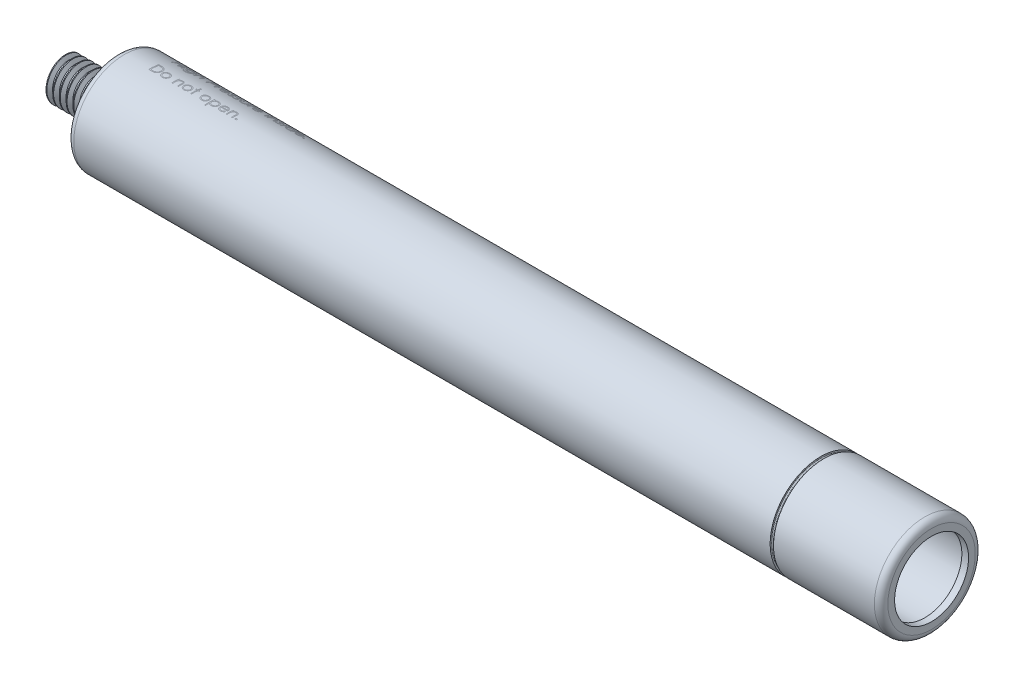
SolidWorks part; units mm, degrees
material "AISI 1020"
ref_plane "Ön Düzlem" through (0, 0, 0) normal (0, 0, 1) x (1, 0, 0)
ref_plane "Üst Düzlem" through (0, 0, 0) normal (0, 1, 0) x (1, 0, 0)
ref_plane "Sağ Düzlem" through (0, 0, 0) normal (1, 0, 0) x (0, 0, -1)
sketch "Çizim1" plane through (0, 0, 0) normal (0, 0, 1) x (1, 0, 0)
  line L0 (0, 3) -> (0, 6.5)
  line L1 (1, 7.5) -> (104.5, 7.5)
  line L8 (0, 0) -> (121, 0) construction
  line L9 (121, 6.5) -> (121, 5.5)
  line L10 (121, 5.5) -> (120, 5.5)
  line L11 (120, 5.5) -> (120, 6)
  line L12 (120, 6) -> (2, 6)
  line L13 (1, 5) -> (1, 0)
  line L14 (105, 7.5) -> (120, 7.5)
  line L16 (104.5, 7.5) -> (104.5, 7.3)
  line L17 (104.65, 7.15) -> (104.85, 7.15)
  line L18 (105, 7.5) -> (105, 7.3)
  line L19 (0, 0) -> (1, 0)
  line L20 (0, 3) -> (-8, 3)
  line L21 (-8, 3) -> (-8, 0)
  line L22 (-8, 0) -> (0, 0)
  arc A0 (120, 7.5) -> (121, 6.5) centre (120, 6.5) cw
  arc A1 (0, 6.5) -> (1, 7.5) centre (1, 6.5) cw
  arc A2 (2, 6) -> (1, 5) centre (2, 5) ccw
  arc A3 (104.5, 7.3) -> (104.65, 7.15) centre (104.65, 7.3) ccw
  arc A4 (104.85, 7.15) -> (105, 7.3) centre (104.85, 7.3) ccw
  point P12 (121, 7.5)
  point P19 (0, 7.5)
  point P28 (104.5, 7.15)
  point P31 (105, 7.15)
  dimension "D9" = 1
  dimension "D10" = 1
  dimension "D13" = 0.15
  dimension "D1" = 121
  dimension "D2" = 7.5
  dimension "D3" = 1.5
  dimension "D4" = 1
  dimension "D5" = 5.5
  dimension "D6" = 1
  dimension "D7" = 0.5
  dimension "D8" = 16
  dimension "D11" = 3
  dimension "D12" = 8
revolve "Döndür1" add sketch "Çizim1" angle 360 about L8
thread "Diş1" pitch 1 method cut trim with start face yes trim with end face yes profile "Diş Profili1" start angle 0, offset 1, length 0, pitch 1, diameter 6
ref_plane "Düzlem1" through (-9, 0, -3) normal (0, -1, 0) x (0, 0, -1)
sketch "Diş Profili1" plane through (-9, 0, -3) normal (0, -1, 0) x (0, 0, -1)
  line L0 (0, 0) -> (0, 1) construction
  line L11 (0, 0) -> (0, 0.875)
  line L12 (0, 0.875) -> (-0.5413, 0.5625)
  line L13 (-0.5413, 0.5625) -> (-0.5413, 0.3125)
  line L15 (-0.5413, 0.3125) -> (0, 0)
  line L17 (-0.5413, 0.4375) -> (0, 0.4375) construction
  point P2 (0, 0)
  dimension "Pitch" = 1
  dimension "Profile_Angle" = 60
  dimension "Profile_Land" = 0.25
  dimension "Profile_Height" = 0.5413
ref_plane "Düzlem2" through (0, 7.5, 0) normal (0, 1, 0) x (1, 0, 0)
sketch "Çizim8" plane through (0, 7.5, 0) normal (0, 1, 0) x (1, 0, 0)
  text T0 "High Pressure inside.\r\nDo not open." font "Century Gothic" height 1.5
wrap "Sar1" sketch "Çizim8" wrap type scribe source sketch "Çizim8" face at (1, 0, 7.5)
